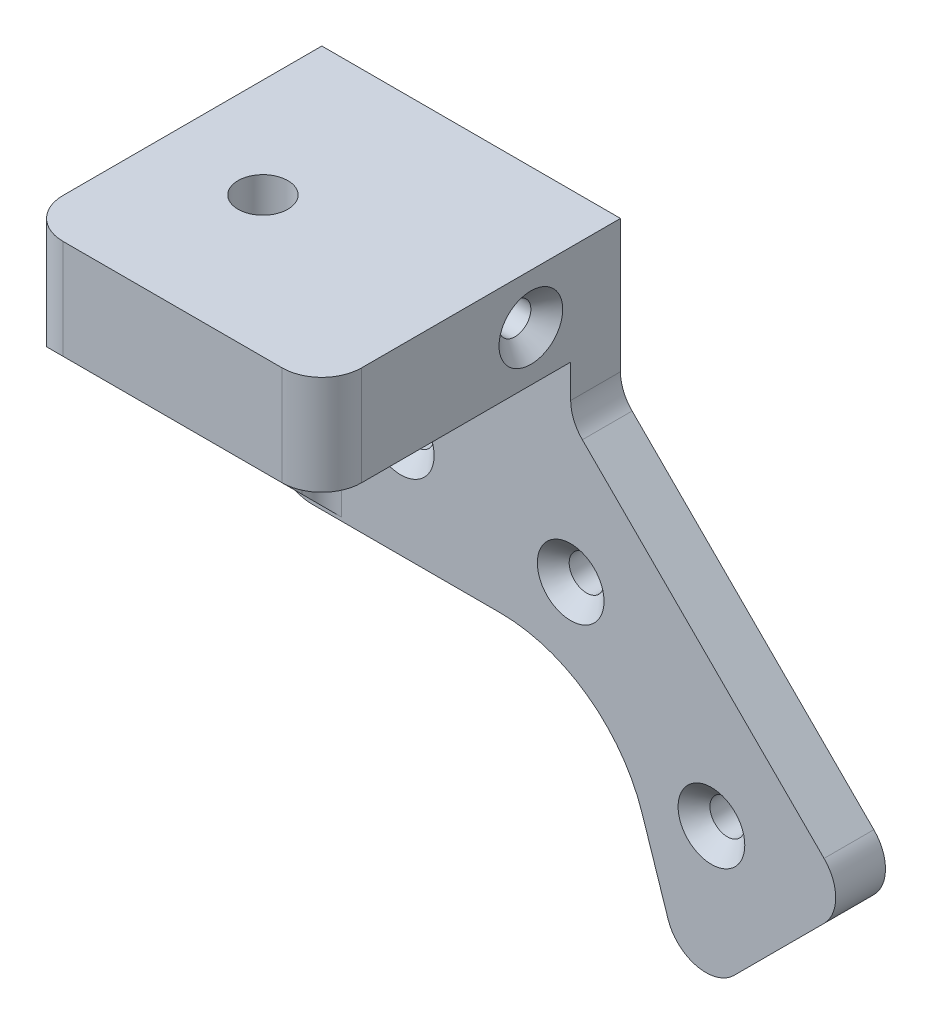
SolidWorks part; units mm, degrees
ref_plane "Front Plane" through (0, 0, 0) normal (0, 0, 1) x (1, 0, 0)
ref_plane "Top Plane" through (0, 0, 0) normal (0, 1, 0) x (1, 0, 0)
ref_plane "Right Plane" through (0, 0, 0) normal (1, 0, 0) x (0, 0, -1)
sketch "Sketch1" plane through (0, 0, 0) normal (0, 0, 1) x (1, 0, 0)
  line L0 (15, 27.5) -> (15, 12.5)
  line L5 (-15, 27.5) -> (15, 27.5)
  line L6 (-15, 27.5) -> (-15, -27.5)
  line L7 (-15, -27.5) -> (15, -27.5)
  line L9 (15, 12.5) -> (43.2843, -15.7843)
  line L10 (-15, -27.5) -> (15, 27.5) construction
  line L11 (43.2843, -15.7843) -> (23.2843, -35.7843)
  line L12 (23.2843, -35.7843) -> (15, -27.5)
  point P0 (0, 0)
  dimension "D1" = 45
  dimension "D2" = 55
  dimension "D3" = 30
  dimension "D4" = 40
  dimension "D5" = 15
extrude "Boss-Extrude1" add sketch "Sketch1" along normal blind 5
sketch "Sketch3" plane through (0, 0, 5) normal (0, 0, 1) x (1, 0, 0)
  line L0 (15, 12.5) -> (15, 27.5) construction
  line L1 (-15, 27.5) -> (15, 27.5)
  line L2 (-15, 27.5) -> (-15, 17.5)
  line L3 (-15, 17.5) -> (15, 17.5)
  line L4 (15, 27.5) -> (15, 17.5)
  dimension "D1" = 10
extrude "Boss-Extrude2" add sketch "Sketch3" along normal blind 25
sketch "Sketch4" plane through (0, 27.5, 0) normal (0, 1, 0) x (1, 0, 0)
  line L0 (-15, -30) -> (-15, 0) construction
  line L1 (15, -30) -> (-15, -30) construction
  line L2 (15, -30) -> (15, -5) construction
  line L3 (15, -5) -> (-15, -5) construction
  line L4 (-15, -30) -> (-15, -5) construction
  line L5 (15, -30) -> (15, 0) construction
  line L6 (-15, 0) -> (15, 0) construction
  line L7 (-15, 0) -> (-15, 5) construction
  line L8 (-15, 5) -> (15, 5) construction
  line L9 (15, 0) -> (15, 5) construction
  line L10 (15, -22.575) -> (-15, -22.575) construction
  circle A0 centre (-5, -15.9175) radius 2.5
  circle A1 centre (-5, -15.9175) radius 6.6575 construction
  circle A2 centre (-5, -16.15) radius 6.425 construction
  dimension "D3" = 13.315
  dimension "D4" = 5
  dimension "D7" = 21.15
  dimension "D8" = 12.85
  dimension "D1" = 25
  dimension "D2" = 5
  dimension "D6" = 20
extrude "Cut-Extrude1" cut sketch "Sketch4" against normal through all
sketch "Sketch6" plane through (-15, 0, 0) normal (-1, 0, 0) x (0, 0, 1)
  line L0 (30, 17.5) -> (5, -7.5)
  line L1 (5, 17.5) -> (5, -27.5) construction
  dimension "D1" = 45
rib "Rib1" sketch "Sketch6" sketch "Sketch6" thickness 5 extrusion direction parallel to sketch draft on no parameters "D1"=5
sketch "Sketch7" plane through (0, 0, 5) normal (0, 0, 1) x (1, 0, 0)
  line L0 (22.1747, -18.1589) -> (26.8198, -32.2487)
  line L1 (-15, -7.8553) -> (7.9289, -7.8553)
  line L2 (-15, -7.8553) -> (-15, -27.5)
  line L3 (-15, -7.5) -> (-15, -27.5) construction
  line L4 (-15, -27.5) -> (15, -27.5) construction
  line L5 (15, 27.5) -> (-15, 27.5) construction
  line L6 (23.2843, -35.7843) -> (43.2843, -15.7843) construction
  line L7 (-15, -27.5) -> (23.2843, -35.7843)
  line L8 (23.2843, -35.7843) -> (26.8198, -32.2487)
  arc A0 (22.1747, -18.1589) -> (7.9289, -7.8553) centre (7.9289, -22.8553) ccw
  circle A1 centre (7.9289, -22.8553) radius 14 construction
  dimension "D1" = 1
  dimension "D2" = 5
extrude "Cut-Extrude2" cut sketch "Sketch7" against normal up to vertex (5 mm away) up to point (-15, -27.5, 0)
sketch "Sketch8" plane through (0, 17.5, 0) normal (0, -1, 0) x (-1, 0, 0)
  line L1 (0.2657, -15.9175) -> (2.6329, -20.0175)
  line L2 (2.6329, -20.0175) -> (7.3671, -20.0175)
  line L3 (7.3671, -20.0175) -> (9.7343, -15.9175)
  line L4 (9.7343, -15.9175) -> (7.3671, -11.8175)
  line L5 (7.3671, -11.8175) -> (2.6329, -11.8175)
  line L6 (2.6329, -11.8175) -> (0.2657, -15.9175)
  circle A0 centre (5, -15.9175) radius 4.1 construction
  dimension "D1" = 8.2
extrude "Cut-Extrude3" cut sketch "Sketch8" against normal blind 5
fillet "Fillet1" radius 4 2 edges at (-15, 22.5, 30) (15, 22.5, 30)
sketch "Sketch9" plane through (0, 0, 5) normal (0, 0, 1) x (1, 0, 0)
  line L0 (15, -1.6421) -> (22.0711, 5.4289) construction
  line L1 (43.2843, -15.7843) -> (15, 12.5) construction
  line L2 (29.1421, -15.7843) -> (36.2132, -8.7132) construction
  line L3 (26.8198, -32.2487) -> (43.2843, -15.7843) construction
  line L4 (15, 12.5) -> (-5.3553, -7.8553) construction
  line L5 (7.9289, -7.8553) -> (-15, -7.8553) construction
  line L6 (15, 12.5) -> (-15, 12.5) construction
  line L7 (-15, 13.5) -> (-15, -7.5) construction
  circle A0 centre (15, -1.6421) radius 1.75
  circle A1 centre (29.1421, -15.7843) radius 1.75
  circle A2 centre (-2.0711, 2.5) radius 1.75
  dimension "D1" = 3.5
  dimension "D5" = 5
  dimension "D2" = 10
  dimension "D3" = 10
  dimension "D4" = 20
  dimension "D6" = 10
extrude "Cut-Extrude4" cut sketch "Sketch9" against normal through all
chamfer "Chamfer1" distance 1.6 angle 45 3 edges at (30.8921, -15.7843, 5) (16.75, -1.6421, 5) (-0.3211, 2.5, 5)
fillet "Fillet2" radius 4 4 edges at (15, 12.5, 2.5) (43.2843, -15.7843, 2.5) (26.8198, -32.2487, 2.5) (-15, -7.8553, 2.5)
sketch "Sketch10" plane through (15, 0, 0) normal (1, 0, 0) x (0, 0, -1)
  line L0 (-9, 17.5) -> (-9, 27.5) construction
  line L1 (-26, 17.5) -> (-5, 17.5) construction
  line L2 (-26, 27.5) -> (0, 27.5) construction
  line L3 (0, 14.1569) -> (0, 27.5) construction
  circle A0 centre (-9, 22.5) radius 1.6
  dimension "D1" = 3.2
  dimension "D2" = 9
extrude "Cut-Extrude5" cut sketch "Sketch10" against normal through all
sketch "Sketch11" plane through (-15, 0, 0) normal (-1, 0, 0) x (0, 0, 1)
  line L1 (10.5877, 19.75) -> (12.1754, 22.5)
  line L2 (12.1754, 22.5) -> (10.5877, 25.25)
  line L3 (10.5877, 25.25) -> (7.4123, 25.25)
  line L4 (7.4123, 25.25) -> (5.8246, 22.5)
  line L5 (5.8246, 22.5) -> (7.4123, 19.75)
  line L6 (7.4123, 19.75) -> (10.5877, 19.75)
  circle A0 centre (9, 22.5) radius 2.75 construction
  dimension "D1" = 5.5
extrude "Cut-Extrude6" cut sketch "Sketch11" against normal blind 4
chamfer "Chamfer2" distance 1.6 angle 45 1 edges at (15, 24.1, 9)
fillet "Fillet3" radius 2 1 edges at (-10, 5, 5)
